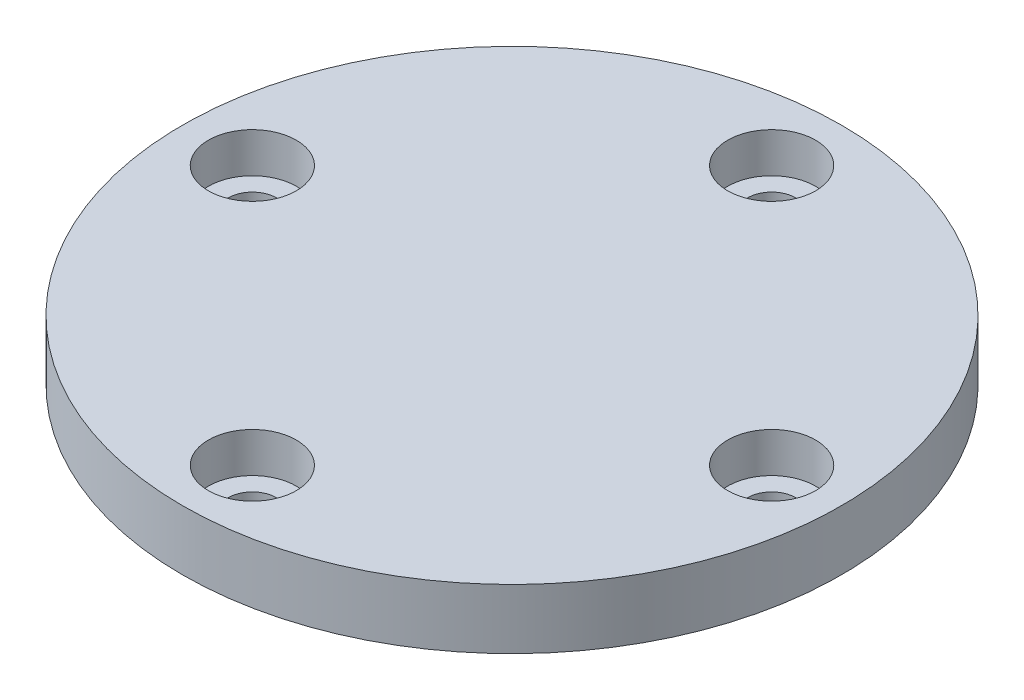
SolidWorks part; units mm, degrees
material "1060 Alloy"
ref_plane "Front Plane" through (0, 0, 0) normal (0, 0, 1) x (1, 0, 0)
ref_plane "Top Plane" through (0, 0, 0) normal (0, 1, 0) x (1, 0, 0)
ref_plane "Right Plane" through (0, 0, 0) normal (1, 0, 0) x (0, 0, -1)
sketch "Sketch1" plane through (0, 0, 0) normal (0, 1, 0) x (1, 0, 0)
  circle A0 centre (0, 0) radius 16.5
  dimension "D1" = 33
extrude "Boss-Extrude1" add sketch "Sketch1" along normal blind 3
sketch "Sketch3" plane through (0, 3, 0) normal (0, 1, 0) x (1, 0, 0)
  circle A0 centre (0, -10.25) radius 0.25
  circle A1 centre (0, 0) radius 9.8
  dimension "D1" = 0.5
  dimension "D2" = 10.25
  dimension "D3" = 19.6
sketch "Sketch4" plane through (0, 3, 0) normal (0, -1, 0) x (1, 0, 0)
  line L0 (0, 0) -> (13.2597, 13.2597) construction
  circle A0 centre (7.7782, 7.7782) radius 1
  dimension "D2" = 2
  dimension "D1" = 11
sketch "Sketch5" plane through (0, 3, 0) normal (0, 1, 0) x (1, 0, 0)
  circle A0 centre (0, 0) radius 11
  dimension "D1" = 22
hole_wizard "CBORE for M2 SHCS1" positions "Sketch6" profile "Sketch7" counterbore size "M2" standard "ANSI Metric" end condition through all
sketch "Sketch6" plane through (0, 3, 0) normal (0, 1, 0) x (1, 0, 0)
  point P0 (13, 0)
  dimension "D1" = 13
sketch "Sketch7" plane through (13, 3, 0) normal (1, 0, 0) x (0, 0, 1)
  line L0 (0, 0) -> (0, 3)
  line L1 (0, 3) -> (1.2, 3)
  line L3 (1.2, 3) -> (1.2, 2)
  line L4 (1.2, 2) -> (2.2, 2)
  line L5 (2.2, 2) -> (2.2, 0)
  line L7 (2.2, 0) -> (0, 0)
  line L11 (0, -6.35) -> (0, 107.95) construction
  dimension "Thru Hole Dia." = 2.4
  dimension "Thru Hole Depth" = 3
  dimension "C'Bore Dia." = 4.4
  dimension "C'Bore Depth" = 2
pattern_circular "CirPattern1" count 4 over 360 about axis through (0, 3, 0) along (0, 1, 0) of "CBORE for M2 SHCS1"
sketch "Sketch8" plane through (0, 0, 0) normal (0, -1, 0) x (1, 0, 0)
  circle A0 centre (0, 0) radius 9
  dimension "D1" = 18
extrude "Boss-Extrude2" add sketch "Sketch8" along normal blind 2
sketch "Sketch9" plane through (0, -2, 0) normal (0, -1, 0) x (1, 0, 0)
  circle A0 centre (6, 0) radius 0.425
  circle A1 centre (0, 0) radius 9 construction
  dimension "D1" = 0.85
  dimension "D2" = 6
extrude "Cut-Extrude1" cut sketch "Sketch9" against normal blind 1.5
